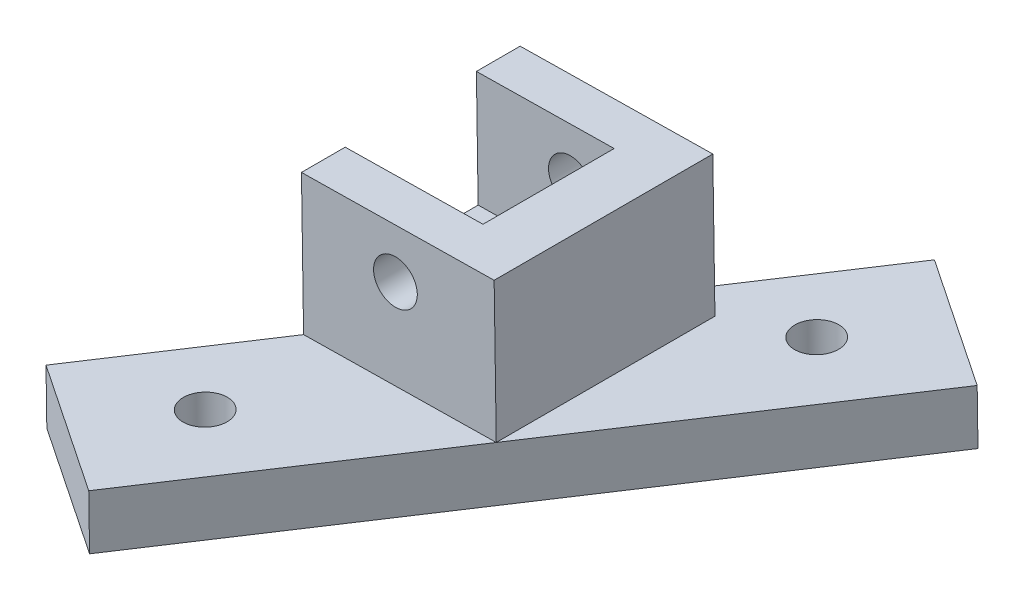
SolidWorks part; units mm, degrees
ref_plane "Front Plane" through (0, 0, 0) normal (0, 0, 1) x (1, 0, 0)
ref_plane "Top Plane" through (0, 0, 0) normal (0, 1, 0) x (1, 0, 0)
ref_plane "Right Plane" through (0, 0, 0) normal (1, 0, 0) x (0, 0, -1)
sketch "Sketch1" plane through (0, 0, 0) normal (0, 0, 1) x (1, 0, 0)
  line L0 (614.2482, 110.6197) -> (642.2246, 111.0468)
  line L1 (604.7125, 110.4741) -> (634.2525, 110.9251) construction
  line L2 (642.2246, 111.0468) -> (642.5336, 90.8054)
  line L3 (642.5336, 90.8054) -> (614.5573, 90.3783)
  line L4 (614.5573, 90.3783) -> (614.2482, 110.6197)
  line L5 (606.4491, 93.8109) -> (623.8845, 94.0771) construction
  line L6 (539.588, 25.7254) -> (651.342, 25.7254) construction
  line L7 (539.588, 25.7254) -> (651.342, 25.7254)
  line L8 (614.5573, 87.1817) -> (642.5336, 87.1817)
  line L9 (642.5336, 87.1817) -> (642.5336, 90.8054)
  line L10 (614.5573, 87.1817) -> (614.5573, 90.3783)
  line L14 (628.0342, 94.4216) -> (630.8108, 94.464)
  line L15 (634.4712, 96.6012) -> (604.3912, 96.1419)
  line L16 (606.4491, 93.8109) -> (623.8845, 94.0771)
  line L17 (628.0342, 94.4216) -> (630.8108, 94.464)
  line L18 (634.4712, 96.6012) -> (604.3912, 96.1419)
  line L19 (606.4491, 93.8109) -> (623.8845, 94.0771)
  arc A0 (634.4712, 96.6012) -> (634.2525, 110.9251) centre (627.8931, 103.6644) ccw construction
  arc A1 (634.2525, 110.9251) -> (634.4712, 96.6012) centre (627.8931, 103.6644) cw
  arc A3 (630.8108, 94.464) -> (634.4712, 96.6012) centre (627.8931, 103.6644) ccw
  arc A4 (630.8108, 94.464) -> (634.4712, 96.6012) centre (627.8931, 103.6644) ccw
  spline S2 degree 3 poles (3530.8695, 754.5018) (777.978, 170.7815) (600.6553, 111.526) (604.4885, 95.4418) (604.5493, 95.2808) (604.6964, 94.9846) (604.783, 94.8489) (604.9677, 94.606) (605.0672, 94.4967) (605.3783, 94.2032) (605.5939, 94.059) (620.5267, 87.2177) (617.3736, 300.9795) (-966.7071, 2645.4273) knots -11.498834 -11.498834 -11.498834 -11.498834 0.125 0.125 0.25 0.25 0.375 0.375 0.5 0.5 0.75 0.75 17.624909 17.624909 17.624909 17.624909 only from (604.3912, 96.1419) to (606.4491, 93.8109)
  spline S3 degree 3 poles (521.0488, 3092.244) (616.5837, 120.4781) (604.5248, 92.0613) (625.1941, 94.1762) (625.5383, 94.219) (626.2378, 94.3007) (626.5912, 94.3393) (659.6185, 97.0046) (727.0183, 17.3746) (1157.1896, -2856.944) knots -14.98138 -14.98138 -14.98138 -14.98138 0.25 0.25 0.5 0.5 0.75 0.75 23.594408 23.594408 23.594408 23.594408 only from (623.8845, 94.0771) to (628.0342, 94.4216)
  spline S4 degree 3 poles (604.3912, 96.1419) (604.3871, 95.9602) (604.4069, 95.7841) (604.4885, 95.4418) (604.5493, 95.2808) (604.6964, 94.9846) (604.783, 94.8489) (604.9677, 94.606) (605.0672, 94.4967) (605.3783, 94.2032) (605.5939, 94.059) (606.0299, 93.8592) (606.244, 93.8078) (606.4491, 93.8109) knots 0 0 0 0 0.125 0.125 0.25 0.25 0.375 0.375 0.5 0.5 0.75 0.75 1 1 1 1
  spline S5 degree 3 poles (623.8845, 94.0771) (624.2015, 94.0819) (624.5265, 94.1079) (625.1941, 94.1762) (625.5383, 94.219) (626.2378, 94.3007) (626.5912, 94.3393) (627.3062, 94.397) (627.6679, 94.416) (628.0342, 94.4216) knots 0 0 0 0 0.25 0.25 0.5 0.5 0.75 0.75 1 1 1 1
  dimension "D2" = 14.4425
  dimension "D1" = 3.556
  dimension "D3" = 0
extrude "Boss-Extrude2" add sketch "Sketch1" against normal up to surface (19.05 mm away) contours S5 L19 L4 L3 L2 L0 A1 A4 L17 region at (638.8344, 100.0611, 0) region at (624.7413, 92.2546, 0)
sketch "Sketch2" plane through (0, 0, 0) normal (0, 0, 1) x (1, 0, 0)
  line L0 (614.5573, 90.3783) -> (614.2482, 110.6197)
  line L1 (604.7125, 110.4741) -> (634.2525, 110.9251) construction
  line L2 (614.2482, 110.6197) -> (642.2246, 111.0468)
  line L3 (642.2246, 111.0468) -> (642.5336, 90.8054)
  line L4 (642.5336, 90.8054) -> (614.5573, 90.3783)
extrude "Boss-Extrude3" add sketch "Sketch2" along normal blind 6.35 contours L4 L0 L2 L3
sketch "Sketch4" plane through (0, 0, -19.05) normal (0, 0, -1) x (-1, 0, 0)
  line L0 (-614.5573, 90.3783) -> (-614.2482, 110.6197)
  line L1 (-604.6203, 110.4727) -> (-634.2525, 110.9251) construction
  line L2 (-614.2482, 110.6197) -> (-642.2246, 111.0468)
  line L3 (-642.2246, 111.0468) -> (-642.5336, 90.8054)
  line L4 (-642.5336, 90.8054) -> (-614.5573, 90.3783)
extrude "Boss-Extrude4" add sketch "Sketch4" along normal blind 6.35
sketch "Sketch5" plane through (0, 0, 0) normal (0, 0, -1) x (-1, 0, 0)
  circle A0 centre (-627.8931, 103.6644) radius 3.175
extrude "Cut-Extrude1" cut sketch "Sketch5" against normal through all
sketch "Sketch6" plane through (0, 0, -19.05) normal (0, 0, 1) x (1, 0, 0)
  circle A0 centre (627.8931, 103.6644) radius 3.175
extrude "Cut-Extrude2" cut sketch "Sketch6" against normal through all
sketch "Sketch9" plane through (0, 0, 6.35) normal (0, 0, 1) x (1, 0, 0)
  line L2 (539.588, 25.7254) -> (651.342, 25.7254) construction
  line L3 (539.588, 25.7254) -> (651.342, 25.7254)
  line L6 (614.5573, 90.3783) -> (642.5336, 90.8054)
  line L7 (614.5573, 80.0701) -> (642.5898, 80.0701)
  line L8 (642.5898, 80.0701) -> (642.5336, 90.8054)
  line L9 (614.5573, 80.0701) -> (614.5573, 90.3783)
sketch "Sketch11" plane through (-1.2363, 80.9766, 0) normal (0.0153, -0.9999, 0) x (0.9999, 0.0153, 0)
  line L0 (615.8653, 6.35) -> (600.7721, 28.6587)
  line L1 (600.7721, 28.6587) -> (619.966, 41.6445)
  line L2 (619.966, 41.6445) -> (643.845, 6.35)
  line L3 (643.845, -25.4) -> (643.845, 6.35) construction
  line L4 (643.845, 6.35) -> (615.8653, 6.35) construction
  line L5 (643.845, 6.35) -> (672.0232, -35.299)
  line L6 (672.0232, -35.299) -> (652.8293, -48.2849)
  line L7 (652.8293, -48.2849) -> (615.8653, 6.35)
  dimension "D1" = 124.081
  dimension "D2" = 90
extrude "Boss-Extrude7" add sketch "Sketch11" along normal blind 7.874
sketch "Sketch12" plane through (-1.2363, 80.9766, 0) normal (-0.0153, 0.9999, 0) x (0.9999, 0.0153, 0)
  line L0 (643.845, -6.35) -> (619.966, -41.6445) construction
  line L1 (672.0232, 35.299) -> (643.845, -6.35) construction
  line L2 (619.966, -41.6445) -> (600.7721, -28.6587) construction
  line L3 (652.8293, 48.2849) -> (672.0232, 35.299) construction
  circle A0 centre (618.1913, -22.9636) radius 3.175
  circle A1 centre (654.0226, 29.9972) radius 3.175
  dimension "D1" = 11.938
  dimension "D2" = 11.938
  dimension "D3" = 14.478
  dimension "D4" = 14.478
extrude "Cut-Extrude4" cut sketch "Sketch12" against normal through all
